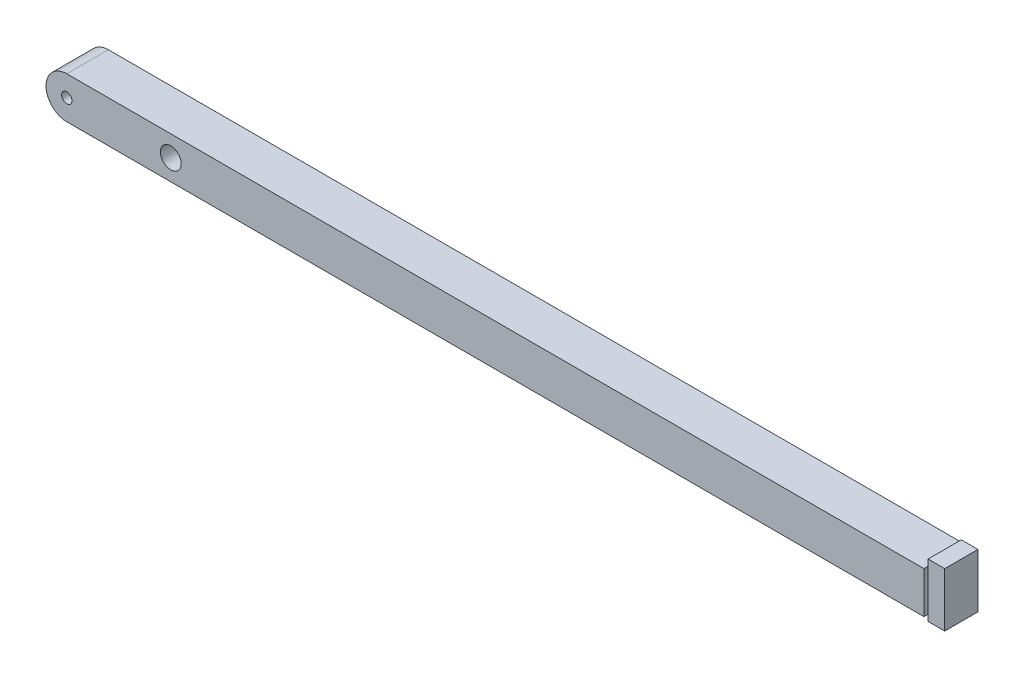
SolidWorks part; units mm, degrees
ref_plane "Front Plane" through (0, 0, 0) normal (0, 0, 1) x (1, 0, 0)
ref_plane "Top Plane" through (0, 0, 0) normal (0, 1, 0) x (1, 0, 0)
ref_plane "Right Plane" through (0, 0, 0) normal (1, 0, 0) x (0, 0, -1)
sketch "Sketch1" plane through (0, 0, 0) normal (0, 0, 1) x (1, 0, 0)
  line L3 (609.6, 25.4) -> (609.6, 0)
  line L20 (76.2, 25.4) -> (139.7, 25.4)
  line L73 (77.3206, 12.7) -> (79.375, 12.7) construction
  line L82 (77.3206, 12.7) -> (79.375, 12.7) construction
  line L201 (76.2, 25.4) -> (609.6, 25.4)
  line L204 (77.3206, 12.7) -> (79.375, 12.7) construction
  line L205 (77.3206, 12.7) -> (79.375, 12.7) construction
  line L206 (77.3206, 12.7) -> (79.375, 12.7) construction
  line L210 (76.2, 0) -> (609.6, 0)
  circle A0 centre (76.2, 12.7) radius 3.175
  circle A1 centre (139.7, 12.7) radius 12.7
  circle A2 centre (139.7, 12.7) radius 6.35
  circle A3 centre (76.2, 12.7) radius 12.7
  dimension "D5" = 25.4
  dimension "D6" = 25.4
  dimension "D7" = 6.35
  dimension "D8" = 12.7
  dimension "D2" = 533.4
  dimension "D3" = 25.4
  dimension "D17" = 63.5
extrude "Boss-Extrude1" add sketch "Sketch1" along normal mid plane 25.4 contours A3 A0 | A3 | A3 | A0 | A3 L210 A1 | A3 A1 | A3 A1 | A3 A1 L20 | A2 | A1 A2 | A1 | A1 | A1 | A1 L201 | A1 L210 | L210 L3 | L3 | L3 L201 region at (379.6285, 12.7, 0) region at (107.95, 12.7, 0) region at (148.4263, 21.4263, 0) region at (84.9263, 21.4263, 0) region at (76.2, 12.7, 0) region at (139.7, 12.7, 0)
extrude "Cut-Extrude3" cut sketch "Sketch1<10>" against normal mid plane 25.4 contours A0 | A2
sketch "Sketch1<10>" plane through (0, 0, 0) normal (0, 0, 1) x (1, 0, 0) same geometry as "Sketch1"
sketch "Sketch2" plane through (609.6, 0, 0) normal (1, 0, 0) x (0, 0, -1)
  line L0 (-12.7, 25.4) -> (-12.7, 0)
  line L1 (-12.7, 0) -> (12.7, 0)
  line L2 (12.7, 0) -> (12.7, 25.4)
  line L3 (12.7, 25.4) -> (-12.7, 25.4)
  line L4 (-10.16, 0) -> (-10.16, 25.4)
  line L5 (10.16, 0) -> (10.16, 25.4)
  line L7 (-10.16, 25.4) -> (10.16, 25.4)
  line L8 (-10.16, 25.4) -> (-10.16, 29.21)
  line L9 (-10.16, 29.21) -> (10.16, 29.21)
  line L10 (10.16, 25.4) -> (10.16, 29.21)
  line L12 (-10.16, 0) -> (10.16, 0)
  line L13 (-10.16, 0) -> (-10.16, -3.81)
  line L14 (-10.16, -3.81) -> (10.16, -3.81)
  line L15 (10.16, 0) -> (10.16, -3.81)
  line M1 (12.7, 0) -> (12.7, 25.4)
  line M2 (12.7, 25.4) -> (-12.7, 25.4)
  line M3 (-12.7, 25.4) -> (-12.7, 0)
  line M4 (-12.7, 0) -> (12.7, 0)
  dimension "D1" = 2.54
  dimension "D2" = 2.54
  dimension "D3" = 3.81
  dimension "D4" = 3.81
extrude "Cut-Extrude4" cut sketch "Sketch2" against normal blind 10.16 contours L4 L3 M4 M3 | L5 M4 M1 M2 region at (609.6, 12.7, 11.43) region at (609.6, 12.7, -11.43)
extrude "Boss-Extrude2" add sketch "Sketch2<3>" against normal blind 10.16 contours L3 L10 L9 L8 | L15 L1 L13 L14 region at (609.6, 27.305, 0) region at (609.6, -1.905, 0)
sketch "Sketch2<3>" plane through (609.6, 0, 0) normal (1, 0, 0) x (0, 0, -1) same geometry as "Sketch2"
